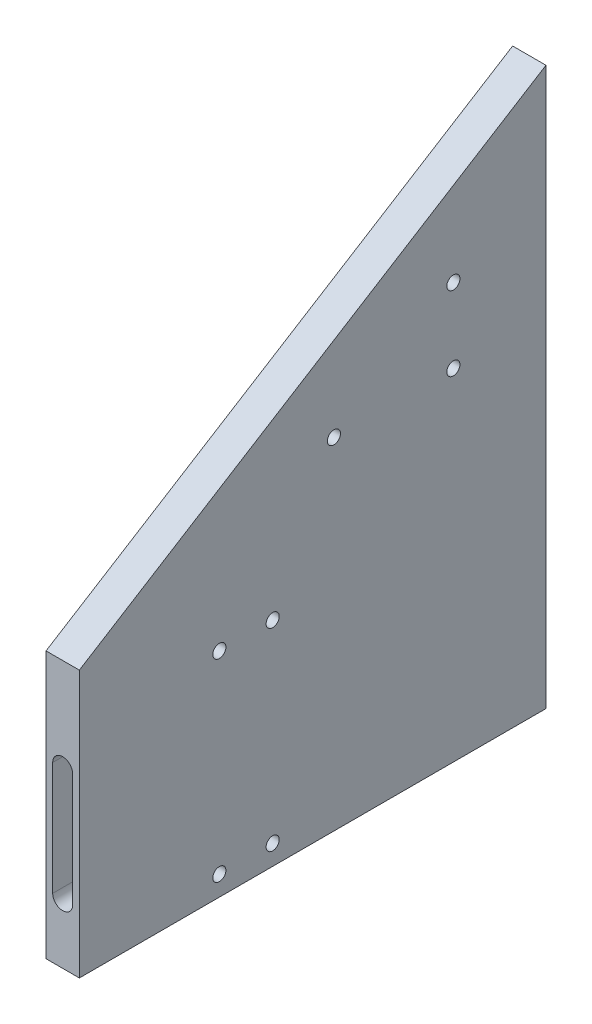
SolidWorks part; units mm, degrees
ref_plane "Front Plane" through (0, 0, 0) normal (0, 0, 1) x (1, 0, 0)
ref_plane "Top Plane" through (0, 0, 0) normal (0, 1, 0) x (1, 0, 0)
ref_plane "Right Plane" through (0, 0, 0) normal (1, 0, 0) x (0, 0, -1)
sketch "Sketch1" plane through (0, 0, 0) normal (0, 0, 1) x (1, 0, 0)
  line L0 (0, 0) -> (0, 88.9)
  line L1 (0, -20.517) -> (0, 20.517) construction
  line L2 (0, 88.9) -> (12.7, 88.9)
  line L3 (12.7, 88.9) -> (12.7, 0)
  line L4 (6.985, 0) -> (-6.985, 0) construction
  line L5 (12.7, 0) -> (0, 0)
  line L7 (6.35, 22.86) -> (6.35, 66.04) construction
  line L8 (2.54, 22.86) -> (2.54, 66.04)
  line L9 (10.16, 22.86) -> (10.16, 66.04)
  line L10 (6.35, 69.85) -> (6.35, 19.05)
  line L11 (12.7, 44.45) -> (0, 44.45)
  arc A0 (2.54, 22.86) -> (10.16, 22.86) centre (6.35, 22.86) ccw
  arc A1 (10.16, 66.04) -> (2.54, 66.04) centre (6.35, 66.04) ccw
  point P13 (6.35, 44.45)
  dimension "D1" = 12.7
  dimension "D2" = 88.9
  dimension "D3" = 50.8
extrude "Boss-Extrude1" add sketch "Sketch1" along normal blind 177.8 contours A1 L9 L11 L3 L2 L0 L8 | A0 L8 L11 L0 L5 L3 L9 region at (6.35, 17.2991, 0) region at (6.35, 71.6009, 0)
sketch "Sketch4" plane through (12.7, 0, 0) normal (1, 0, 0) x (0, 0, -1)
  line L0 (0, 88.9) -> (-177.8, 88.9)
  line L1 (0, 6.985) -> (0, -6.985) construction
  line L3 (-88.9, 88.9) -> (-88.9, 0)
  line L4 (-114.3, 88.9) -> (-114.3, 0)
  line L5 (-114.3, 88.9) -> (-114.3, 81.28)
  line L6 (6.985, 0) -> (-6.985, 0) construction
  line L7 (-114.3, 0) -> (-114.3, 7.62)
  line L8 (-114.3, 81.28) -> (-124.46, 81.28)
  line L9 (-114.3, 81.28) -> (-104.14, 81.28)
  line L10 (-114.3, 7.62) -> (-104.14, 7.62)
  line L11 (-114.3, 7.62) -> (-124.46, 7.62)
  point P11 (-104.14, 81.28)
  point P15 (-124.46, 81.28)
  point P16 (-104.14, 7.62)
  point P18 (-124.46, 7.62)
  dimension "D4" = 10.16
  dimension "D5" = 73.66
sketch "Sketch5" plane through (0, 0, 0) normal (1, 0, 0) x (0, 0, -1)
  line L0 (-177.8, 88.9) -> (-177.8, 101.6)
  line L1 (0, 212.3094) -> (0, 88.9)
  line L2 (-177.8, 101.6) -> (0, 212.3094)
  line L3 (-177.8, 101.6) -> (0, 101.6)
  line L4 (0, 101.6) -> (-49.6751, 181.3786)
  line L5 (-49.6751, 181.3786) -> (-46.3187, 175.9881)
  line L6 (-46.3187, 175.9881) -> (-3.3564, 106.9904)
  line L7 (-3.3564, 106.9904) -> (0, 101.6)
  line L8 (-46.3187, 175.9881) -> (0, 204.8291)
  line L9 (0, 204.8291) -> (0, 109.0804)
  line L10 (0, 109.0804) -> (-3.3564, 106.9904)
  line L11 (-3.3564, 106.9904) -> (-12.0135, 101.6)
  line L12 (-177.8, 88.9) -> (0, 88.9)
  line L13 (-46.3187, 175.9881) -> (-88.9047, 149.4714)
  line L15 (-88.9047, 149.4714) -> (-165.7865, 101.6)
  dimension "D1" = 93.98
  dimension "D3" = 6.35
  dimension "D4" = 6.35
  dimension "D2" = 12.7
  dimension "D5" = 165.7865
ref_plane "Plane1" through (12.7, 0, 0) normal (1, 0, 0) x (0, 0, -1)
sketch "Sketch6" plane through (12.7, 0, 0) normal (1, 0, 0) x (0, 0, -1)
  line L0 (-177.8, 88.9) -> (-177.8, 101.6)
  line L1 (0, 212.3094) -> (0, 88.9)
  line L2 (-177.8, 101.6) -> (0, 212.3094)
  line L3 (-177.8, 101.6) -> (0, 101.6)
  line L4 (0, 101.6) -> (-49.6751, 181.3786)
  line L5 (-49.6751, 181.3786) -> (-46.3187, 175.9881)
  line L6 (-46.3187, 175.9881) -> (-3.3564, 106.9904)
  line L7 (-3.3564, 106.9904) -> (0, 101.6)
  line L8 (-46.3187, 175.9881) -> (0, 204.8291)
  line L9 (0, 204.8291) -> (0, 109.0804)
  line L10 (0, 109.0804) -> (-3.3564, 106.9904)
  line L11 (-3.3564, 106.9904) -> (-12.0135, 101.6)
  line L12 (-177.8, 88.9) -> (0, 88.9)
  line L13 (-46.3187, 175.9881) -> (-88.9047, 149.4714)
  line L15 (-88.9047, 149.4714) -> (-165.7865, 101.6)
extrude "Boss-Extrude2" add sketch "Sketch5" along normal up to surface (12.7 mm away) contours L0 L12 L1 L3 | L15 L13 L4 L2 L3 | L4 L8 L1 L2 region at (0, 95.25, 88.9) region at (0, 140.1574, 109.9399) region at (0, 193.6638, 24.0082) up to face at (12.7, 44.45, 88.9)
extrude "Boss-Extrude4" add sketch "Sketch6" against normal blind 4.445 contours L13 L15 L3 L11 L4 | L10 L1 L8 L4 | L4 L11 L3 | L1 L10 L4 region at (12.7, 126.5174, 71.0479) region at (12.7, 105.8903, 1.1188) region at (12.7, 103.3968, 5.1233) region at (12.7, 161.0956, 15.5152)
extrude "Boss-Extrude5" add sketch "Sketch5<6>" along normal blind 4.445 contours L13 L15 L3 L11 L4 | L10 L1 L8 L4 | L4 L11 L3 | L1 L10 L4 region at (0, 126.5174, 71.0479) region at (0, 105.8903, 1.1188) region at (0, 103.3968, 5.1233) region at (0, 161.0956, 15.5152)
sketch "Sketch5<6>" plane through (0, 0, 0) normal (1, 0, 0) x (0, 0, -1) same geometry as "Sketch5"
sketch "Sketch7" plane through (0, 0, 0) normal (1, 0, 0) x (0, 0, -1)
  line L0 (0, 212.3094) -> (-49.6751, 181.3786)
  line L1 (-49.6751, 181.3786) -> (-35.2872, 158.2714)
  line L2 (0, 101.6) -> (-49.6751, 181.3786) construction
  line L3 (-35.2872, 158.2714) -> (-35.2872, 101.6)
  line L4 (-177.8, 101.6) -> (0, 101.6) construction
  line L5 (-35.2872, 158.2714) -> (-126.3018, 101.6)
  line L6 (-80.7945, 129.9357) -> (-95.1825, 153.0429)
  line L7 (-177.8, 101.6) -> (0, 212.3094) construction
  line L8 (-95.1825, 153.0429) -> (-49.6751, 181.3786)
  line L9 (-35.2872, 129.9357) -> (-80.7945, 129.9357)
  point P4 (-80.7945, 129.9357)
  point P5 (-35.2872, 158.2714)
  point P15 (-35.2872, 129.9357)
hole_wizard "M6x1.0 Tapped Hole1" positions "Sketch4" profile "Sketch10" tap size "M6x1.0" standard "ANSI Metric" end condition through all
sketch "Sketch10" plane through (12.7, 7.62, 124.46) normal (0, 1, 0) x (0, 0, -1)
  line L0 (0, 0) -> (0, 12.7)
  line L1 (0, 12.7) -> (2.5, 12.7)
  line L2 (2.5, 12.7) -> (2.5, 0)
  line L5 (2.5, 0) -> (0, 0)
  line L11 (0, -6.35) -> (0, 107.95) construction
  dimension "Thru Tap Drill Dia." = 5
  dimension "Thru Tap Drill Depth" = 12.7
cosmetic thread "Hole Thread4" parameters "D2"=6
cosmetic thread "Hole Thread5" parameters "D2"=6
cosmetic thread "Hole Thread6" parameters "D2"=6
cosmetic thread "Hole Thread7" parameters "D2"=6
hole_wizard "M6x1.0 Tapped Hole2" positions "Sketch7" profile "Sketch11" tap size "M6x1.0" standard "ANSI Metric" end condition through all
sketch "Sketch11" plane through (0, 129.9357, 35.2872) normal (0, 1, 0) x (0, 0, 1)
  line L0 (0, 0) -> (0, 12.7)
  line L1 (0, 12.7) -> (2.5, 12.7)
  line L2 (2.5, 12.7) -> (2.5, 0)
  line L5 (2.5, 0) -> (0, 0)
  line L11 (0, -6.35) -> (0, 107.95) construction
  dimension "Thru Tap Drill Dia." = 5
  dimension "Thru Tap Drill Depth" = 12.7
cosmetic thread "Hole Thread1" parameters "D2"=6
cosmetic thread "Hole Thread2" parameters "D2"=6
cosmetic thread "Hole Thread3" parameters "D2"=6
equation "\"plateheight\"= 3.5in"
equation "\"platethickness\"= 0.5in"
equation "\"brakedplatethickness\"= 0.25in"
equation "\"brakedplateheight\"= 3in"
equation "\"axlemounttolerance\"= 0.1in"
equation "\"brakedplatetolerance\"= 0.1in"
equation "\"beltholethickness\"= 0.3in"
equation "\"beltholeheight\"= 2in"
equation "\"waistcentertohipoffsetaverage\"= 1in'posterior distance of center of axle mount from center of plate"
equation "\"screwholeheightoffset\"= 0.3in'difference between upper/lower faces of flat plate and the screw holes for the axle mount"
equation "\"D1@Sketch1\"=\"platethickness\""
equation "\"D2@Sketch1\"=\"plateheight\""
equation "\"D3@Sketch1\"=\"beltholeheight\""
equation "\"D4@Sketch1\"=\"beltholethickness\""
equation "\"platedepth\"= 7in'take smallest waist depth 7.4in and subtract 0.4in"
equation "\"D1@Boss-Extrude1\"=\"platedepth\""
equation "\"D2@Sketch4\"=\"screwholeheightoffset\""
equation "\"D3@Sketch4\"=\"screwholeheightoffset\""
equation "\"brakedplatematethickness\"= 0.25in'diffrence from both edges to braked plate"
equation "\"D1@Sketch5\"=(\"brakedplateheight\"+2*(\"brakedplatetolerance\")+2*(\"brakedplatethickness\"))"
equation "\"D3@Sketch5\"=\"brakedplatematethickness\""
equation "\"D4@Sketch5\"=\"brakedplatematethickness\""
equation "\"brakedplateholemargin\"= 0.5in'extra vertical bit to transition between plate and braked plate mount"
equation "\"D2@Sketch5\"=\"brakedplateholemargin\""
equation "\"D1@Boss-Extrude3\"= ( \"platethickness\" - \"brakedplatethickness\" ) / 2"
equation "\"D1@Boss-Extrude4\"=(\"platethickness\"-\"brakedplatethickness\"+\"brakedplatetolerance\")/2"
equation "\"D1@Boss-Extrude5\"=(\"platethickness\"-\"brakedplatethickness\"+\"brakedplatetolerance\")/2"
equation "\"D1@Sketch4\"=\"waistcentertohipoffsetaverage\""
equation "\"rodmountwidth\"= 1.5in"
equation "\"screwholewidthoffset\"= 0.35in"
equation "\"D4@Sketch4\"=(\"rodmountwidth\"/2)-\"screwholewidthoffset\""
